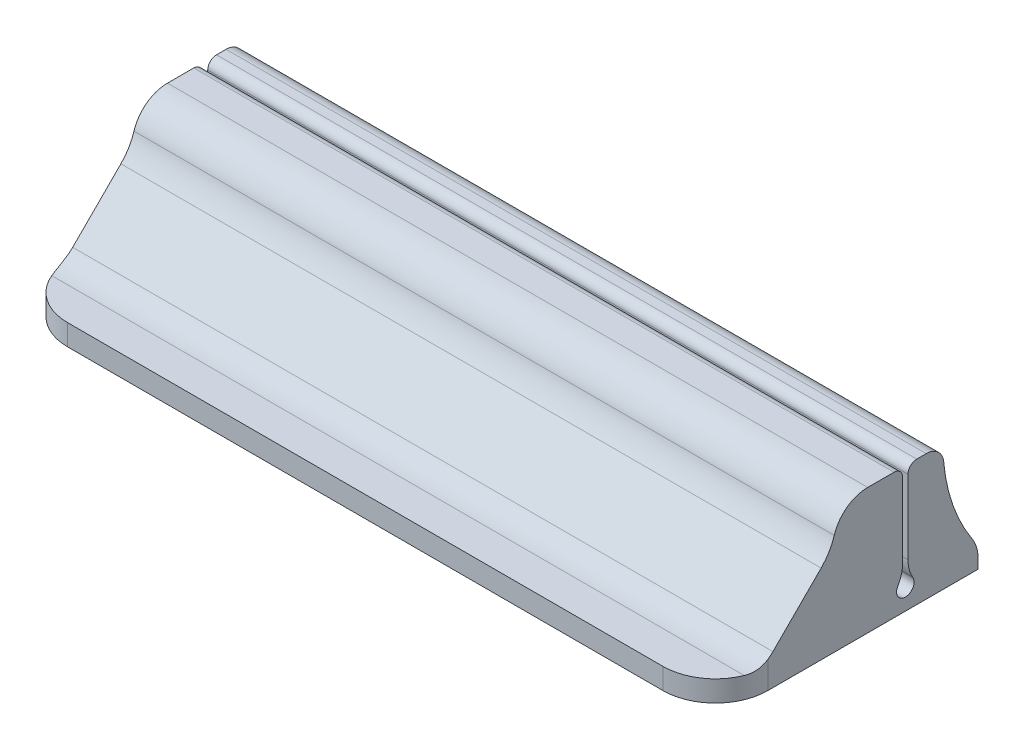
SolidWorks part; units mm, degrees
ref_plane "前视基准面" through (0, 0, 0) normal (0, 0, 1) x (1, 0, 0)
ref_plane "上视基准面" through (0, 0, 0) normal (0, 1, 0) x (1, 0, 0)
ref_plane "右视基准面" through (0, 0, 0) normal (1, 0, 0) x (0, 0, -1)
other "Configuration Table"
sketch "草图1" plane through (0, 0, 0) normal (0, 1, 0) x (1, 0, 0)
  line L1 (-20, 7.5) -> (20, 7.5)
  line L2 (-20, 7.5) -> (-20, -7.5)
  line L3 (-20, -7.5) -> (20, -7.5)
  line L4 (20, 7.5) -> (20, -7.5)
  line L5 (-20, 7.5) -> (20, -7.5) construction
  line L6 (-20, -7.5) -> (20, 7.5) construction
  point P0 (0, 0)
  dimension "D1" = 40
  dimension "D2" = 15
extrude "凸台-拉伸1" add sketch "草图1" along normal blind 1.2
sketch "草图2" plane through (0, 1.2, 0) normal (0, 1, 0) x (1, 0, 0)
  line L0 (-20, 7.5) -> (-20, -7.5) construction
  line L1 (-20, 5.5) -> (20, 5.5)
  line L2 (-20, 5.5) -> (-20, 3.5)
  line L3 (-20, 3.5) -> (20, 3.5)
  line L4 (20, 5.5) -> (20, 3.5)
  line L5 (20, -7.5) -> (20, 7.5) construction
  line L6 (20, 7.5) -> (-20, 7.5) construction
  line L7 (-20, 3.2) -> (20, 3.2)
  line L8 (-20, 3.2) -> (-20, -0.8)
  line L9 (-20, -0.8) -> (20, -0.8)
  line L10 (20, 3.2) -> (20, -0.8)
  dimension "D1" = 2
  dimension "D2" = 2
  dimension "D3" = 0.3
  dimension "D4" = 4
extrude "凸台-拉伸2" add sketch "草图2" along normal blind 6
fillet "圆角1" radius 10 1 edges at (0, 1.2, -5.5)
chamfer "倒角1" distance 4 angle 45 1 edges at (0, 1.2, 0.8)
fillet "圆角2" radius 2 2 edges at (0, 1.2, 4.8) (0, 7.2, 0.8)
fillet "圆角3" radius 0.5 2 edges at (0, 7.2, -3.5) (0, 7.2, -3.2)
sketch "草图3" plane through (20, 0, 0) normal (1, 0, 0) x (0, 0, -1)
  line L0 (3.2, 1.2) -> (3.5, 1.2) construction
  circle A0 centre (3.35, 1.2) radius 0.5
  dimension "D1" = 1
extrude "切除-拉伸1" cut sketch "草图3" against normal up to next
fillet "圆角4" radius 1 1 edges at (0, 7.2, -5.5)
fillet "圆角5" radius 2 1 edges at (0, 1.2, -7.5)
fillet "圆角6" radius 3 1 edges at (0, 5.2, 0.8)
fillet "圆角7" radius 2 2 edges at (0, 1.677, -3.2) (0, 1.677, -3.5)
fillet "圆角8" radius 3 2 edges at (20, 0.6, 7.5) (-20, 0.6, 7.5)
